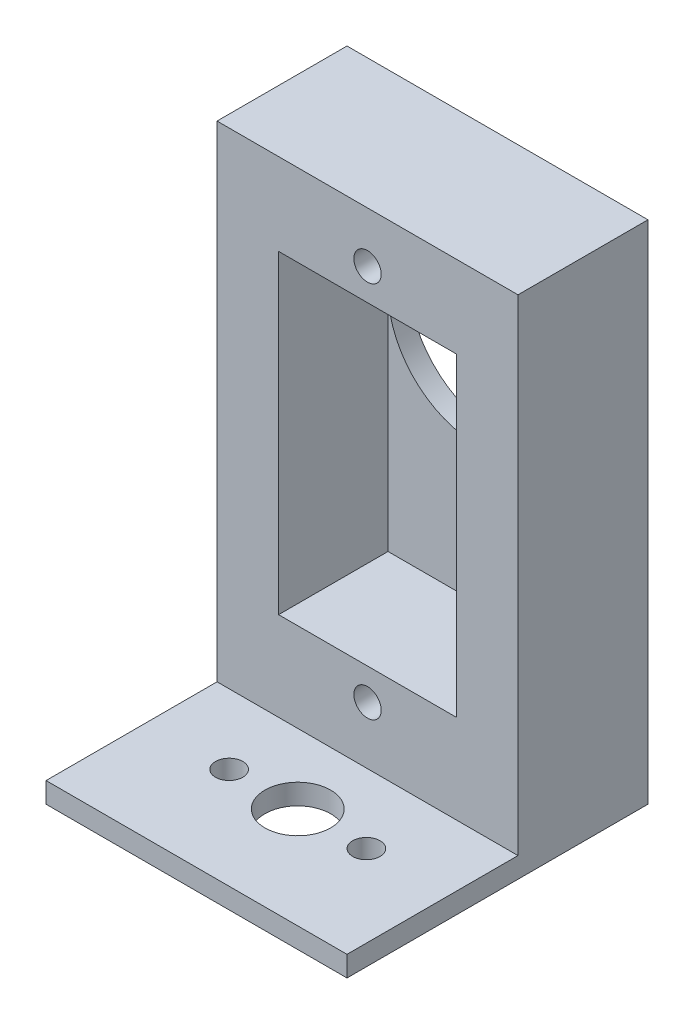
SolidWorks part; units mm, degrees
ref_plane "Front Plane" through (0, 0, 0) normal (0, 0, 1) x (1, 0, 0)
ref_plane "Top Plane" through (0, 0, 0) normal (0, 1, 0) x (1, 0, 0)
ref_plane "Right Plane" through (0, 0, 0) normal (1, 0, 0) x (0, 0, -1)
sketch "Sketch1" plane through (0, 0, 0) normal (0, 1, 0) x (1, 0, 0)
  line L1 (-11, -11) -> (11, -11)
  line L2 (-11, -11) -> (-11, 11)
  line L3 (-11, 11) -> (11, 11)
  line L4 (11, -11) -> (11, 11)
  line L5 (-11, -11) -> (11, 11) construction
  line L6 (-11, 11) -> (11, -11) construction
  point P0 (0, 0)
  dimension "D1" = 22
  dimension "D2" = 22
extrude "Boss-Extrude1" add sketch "Sketch1" along normal blind 37
sketch "Sketch3" plane through (11, 0, 0) normal (1, 0, 0) x (0, 0, -1)
  line L3 (11, 37) -> (8.5, 37)
  line L4 (11, 37) -> (11, 19)
  line L5 (11, 19) -> (8.5, 19)
  line L6 (8.5, 37) -> (8.5, 19)
  line L7 (-11, 37) -> (1.5, 46)
  line L8 (-11, 37) -> (-11, 1.5)
  line L9 (-11, 1.5) -> (1.5, 1.5)
  line L10 (1.5, 46) -> (1.5, 1.5)
  point P9 (1.5, 46)
  point P12 (-11, 46)
  line M11 (11, 37) -> (-11, 37)
  line M12 (-11, 37) -> (-11, 0)
  dimension "D3" = 2.5
  dimension "D4" = 18
extrude "Cut-Extrude2" cut sketch "Sketch3" against normal through all contours L10 L9 M11 M12 region at (11, 19.25, 4.75)
sketch "Sketch9" plane through (0, 0, -1.5) normal (0, 0, 1) x (1, 0, 0)
  line L0 (-11, 1.5) -> (11, 1.5) construction
  line L1 (-6.5, 8) -> (6.5, 8)
  line L2 (-6.5, 8) -> (-6.5, 31)
  line L3 (-6.5, 31) -> (6.5, 31)
  line L4 (6.5, 8) -> (6.5, 31)
  line L5 (-6.5, 8) -> (6.5, 31) construction
  line L6 (-6.5, 31) -> (6.5, 8) construction
  point P0 (0, 19.5)
  dimension "D1" = 13
  dimension "D2" = 23
  dimension "D3" = 6.5
sketch "Sketch18" plane through (0, 1.5, 0) normal (0, 1, 0) x (1, 0, 0)
  circle A0 centre (0, -3.5999) radius 2.4
  circle A1 centre (5.0159, -3.5999) radius 1
  circle A2 centre (-5.0159, -3.5999) radius 1
extrude "Cut-Extrude10" cut sketch "Sketch18" against normal through all
extrude "Cut-Extrude4" cut sketch "Sketch9" against normal blind 8
sketch "Sketch10" plane through (0, 0, -9.5) normal (0, 0, 1) x (1, 0, 0)
  line L1 (6.5, 31) -> (-6.5, 31) construction
  circle A0 centre (0, 24.5) radius 6.5
  dimension "D1" = 13
  dimension "D2" = 6.5
extrude "Cut-Extrude5" cut sketch "Sketch10" against normal through all
sketch "Sketch11" plane through (0, 0, -1.5) normal (0, 0, 1) x (1, 0, 0)
  line L1 (6.5, 31) -> (0, 31) construction
  circle A0 centre (0, 33.3) radius 1
  circle A1 centre (0, 5.7) radius 1
  dimension "D1" = 27.6
  dimension "D2" = 2
  dimension "D3" = 2
  dimension "D4" = 2.3
extrude "Cut-Extrude6" cut sketch "Sketch11" against normal blind 8
